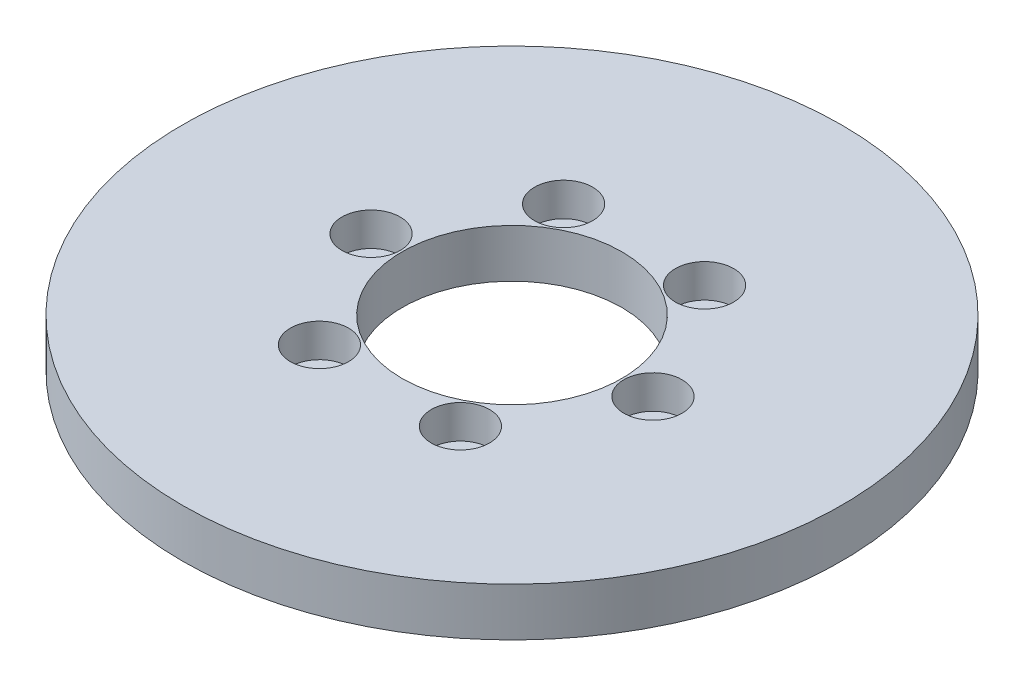
SolidWorks part; units mm, degrees
ref_plane "Front Plane" through (0, 0, 0) normal (0, 0, 1) x (1, 0, 0)
ref_plane "Top Plane" through (0, 0, 0) normal (0, 1, 0) x (1, 0, 0)
ref_plane "Right Plane" through (0, 0, 0) normal (1, 0, 0) x (0, 0, -1)
sketch "Sketch1" plane through (0, 0, 0) normal (0, 1, 0) x (1, 0, 0)
  circle A0 centre (0, 0) radius 75
  dimension "FLANGE_OD" = 150
extrude "Boss-Extrude1" add sketch "Sketch1" along normal blind 11
sketch "Sketch2" plane through (0, 0, 0) normal (0, 1, 0) x (1, 0, 0)
  circle A0 centre (0, 0) radius 25
  dimension "BORE_D" = 50
extrude "Cut-Extrude1" cut sketch "Sketch2" along normal through all
sketch "Sketch3" plane through (0, 11, 0) normal (0, 1, 0) x (1, 0, 0)
  circle A0 centre (0, 0) radius 32.078 construction
  circle A1 centre (-32.078, 0) radius 6.6218
  dimension "BOLT_D" = 13.2437
  dimension "BOLT_PCD" = 64.156
extrude "Cut-Extrude2" cut sketch "Sketch3" against normal blind 7.6025
pattern_circular "CirPattern1" count 6 over 360 about axis through (0, 0, 0) along (0, 1, 0) of "Cut-Extrude2"
